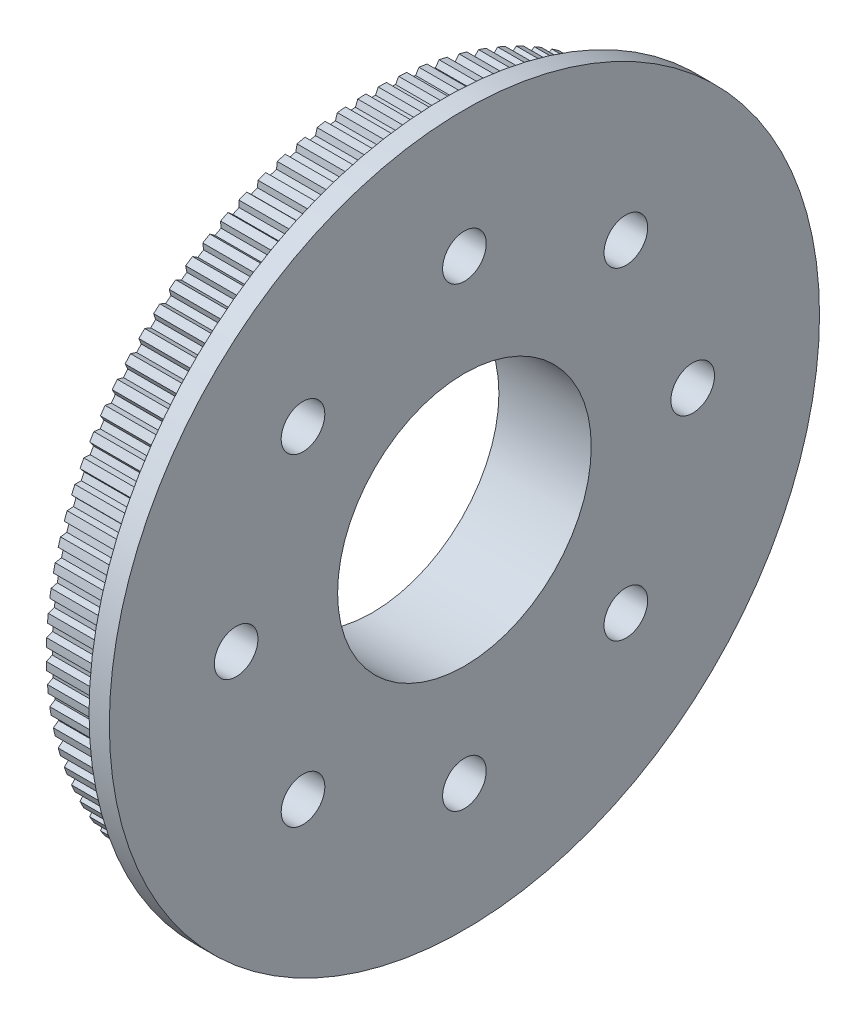
SolidWorks part; units mm, degrees
ref_plane "Front Plane" through (0, 0, 0) normal (0, 0, 1) x (1, 0, 0)
ref_plane "Top Plane" through (0, 0, 0) normal (0, 1, 0) x (1, 0, 0)
ref_plane "Right Plane" through (0, 0, 0) normal (1, 0, 0) x (0, 0, -1)
sketch "Sketch2" plane through (0, 0, 0) normal (1, 0, 0) x (0, 0, -1)
  line L3 (0, 0) -> (0, 31.5245) construction
  line L6 (0, -32.0325) -> (0, -32.35) construction
  line L7 (-0.5715, 32.0274) -> (-0.3362, 31.5227)
  line L8 (0.5715, 32.0274) -> (0.3362, 31.5227)
  line L9 (-0.5715, 32.0274) -> (-0.6449, 32.1848)
  line L10 (0.5715, 32.0274) -> (0.6449, 32.1848)
  line L12 (-0.3362, 31.5227) -> (0.3362, 31.5227)
  line L14 (0, 32.0325) -> (0, 32.35) construction
  line L15 (0, 0) -> (0, -1.143) construction
  circle A0 centre (0, 0) radius 32.35 construction
  circle A1 centre (0, 0) radius 31.5245 construction
  circle A2 centre (0, 0) radius 32.0325 construction
  arc A7 (0.6449, 32.1848) -> (-0.6449, 32.1848) centre (0, 0) ccw
  point P5 (0, 32.1913)
  dimension "D1" = 50
  dimension "D2" = 0.3175
sketch "Sketch1" plane through (0, 0, 0) normal (0, 0, 1) x (1, 0, 0)
  line L0 (-9.55, 0) -> (9.55, 0) construction
  line L1 (-9.55, 4) -> (9.55, 4)
  line L2 (-9.55, 4) -> (-9.55, 19.05)
  line L3 (-9.55, 19.05) -> (0.05, 19.05)
  line L5 (0.05, 19.05) -> (0.05, 32.1)
  line L9 (0.05, 32.1) -> (9.55, 32.1)
  line L10 (9.55, 32.1) -> (9.55, 4)
  line L12 (-4.75, 19.05) -> (-4.75, 4) construction
  point P7 (9.55, 32.1)
  dimension "Bore Size" = 8
  dimension "Overall Width" = 19.1
  dimension "Outside Width" = 9.5
  dimension "Hub Dia" = 38.1
  dimension "OD" = 64.2
revolve "Revolve1" add sketch "Sketch1" angle 360 mid plane about L0
sketch "Sketch3" plane through (0.05, 0, 0) normal (-1, 0, 0) x (0, 0, 1)
  line L3 (0.3362, 31.5227) -> (-0.3362, 31.5227) construction
  line L5 (-0.6449, 32.1848) -> (-0.3362, 31.5227)
  line L6 (-0.3362, 31.5227) -> (0.3362, 31.5227)
  line L7 (0.6449, 32.1848) -> (0.3362, 31.5227)
  arc A1 (0.6449, 32.1848) -> (-0.6449, 32.1848) centre (0, 0) ccw construction
  arc A2 (0.6449, 32.1848) -> (-0.6449, 32.1848) centre (0, 0) ccw
extrude "Cut-Extrude1" cut sketch "Sketch3" along normal through all both and the other way through all
pattern_circular "CirPattern1" count 100 over 360 about axis through (-9.55, 0, 0) along (-1, 0, 0) of "Cut-Extrude1" reverse direction yes
sketch "Sketch5" plane through (0, 0, 0) normal (0, 0, 1) x (1, 0, 0)
  point P0 (0, 0)
sketch "Sketch6" plane through (0, 0, 0) normal (0, 1, 0) x (1, 0, 0)
  line L0 (-9.55, 0) -> (-6.775, 0) construction
  line L1 (-9.55, 19.05) -> (-9.55, -19.05) construction
  line L2 (0, 0) -> (-2.775, 0) construction
  circle A0 centre (-4.775, 0) radius 2 construction
  circle A1 centre (-4.775, 0) radius 2.1
  dimension "D1" = 0.1
  dimension "SS Dia" = 4
extrude "Cut-Extrude3" cut sketch "Sketch6" along normal through all
sketch "Sketch7" plane through (0, 0, 0) normal (0, 0, 1) x (1, 0, 0)
  line L0 (-6.521, 19.05) -> (-4.775, 19.05)
  line L1 (-6.775, 18.796) -> (-6.775, 4.635)
  line L2 (-6.775, 4.635) -> (-6.521, 4.381)
  line L3 (-6.521, 4.381) -> (-4.775, 4.381)
  line L4 (-4.775, 4.381) -> (-4.775, 19.05) construction
  line L5 (-2.675, 0) -> (-6.875, 0) construction
  line L6 (-6.775, 18.796) -> (-6.521, 19.05)
  line L7 (-9.55, 19.05) -> (0.05, 19.05) construction
  line L8 (-4.775, 19.05) -> (-4.775, 4.381)
  line L9 (-2.675, 0) -> (-6.875, 0) construction
  line L10 (-4.775, 0) -> (-5.825, -1.8187) construction
  circle A0 centre (-4.775, 0) radius 2.1 construction
  point P0 (-6.775, 19.05)
  point P4 (-6.775, 4.381)
  point P17 (-5.825, -1.8187)
  dimension "D1" = 60
  dimension "D2" = 0.381
revolve "Revolve2" add sketch "Sketch7" angle 360 mid plane about L4
sketch "Sketch8" plane through (0, 19.05, 0) normal (0, 1, 0) x (1, 0, 0)
  line L1 (-4.775, 0.866) -> (-5.525, 0.433)
  line L2 (-5.525, 0.433) -> (-5.525, -0.433)
  line L3 (-5.525, -0.433) -> (-4.775, -0.866)
  line L4 (-4.775, -0.866) -> (-4.025, -0.433)
  line L5 (-4.025, -0.433) -> (-4.025, 0.433)
  line L6 (-4.025, 0.433) -> (-4.775, 0.866)
  circle A0 centre (-4.775, 0) radius 0.75 construction
  dimension "D1" = 1.5
extrude "Cut-Extrude4" cut sketch "Sketch8" against normal blind 1.016
pattern_circular "CirPattern2" count 2 over 90 about axis through (-9.55, 0, 0) along (-1, 0, 0) of "Cut-Extrude3" reverse direction yes
pattern_circular "CirPattern3" count 2 over 90 about axis through (-9.55, 0, 0) along (-1, 0, 0) reverse direction yes of bodies 107
chamfer "Chamfer1" distance 0.5 angle 45 1 edges at (-9.55, 0, 4)
chamfer "Chamfer2" distance 0.5 angle 45 1 edges at (-9.55, 0, 19.05)
chamfer "Chamfer3" distance 0.5 angle 45 1 edges at (9.55, 0, 4)
sketch "Sketch9" plane through (0, 0, 0) normal (1, 0, 0) x (0, 0, -1)
  circle A0 centre (0, 0) radius 32.1 construction
sketch "Sketch10" plane through (-9.55, 0, 0) normal (-1, 0, 0) x (0, 0, 1)
  circle A0 centre (0, 0) radius 56.9699
extrude "Cut-Extrude5" cut sketch "Sketch10" against normal blind 12
sketch "Sketch13" plane through (9.55, 0, 0) normal (1, 0, 0) x (0, 0, -1)
  circle A0 centre (0, 0) radius 35
  dimension "D1" = 70
extrude "Boss-Extrude1" add sketch "Sketch13" along normal blind 2
sketch "Sketch11" plane through (2.45, 0, 0) normal (-1, 0, 0) x (0, 0, 1)
  circle A0 centre (0, 0) radius 12.5
  dimension "D1" = 25
extrude "Cut-Extrude6" cut sketch "Sketch11" against normal through all
sketch "Sketch12" plane through (2.45, 0, 0) normal (-1, 0, 0) x (0, 0, 1)
  line L0 (0, 0) -> (0, 22.5) construction
  circle A0 centre (0, 22.5) radius 2.15
  dimension "D2" = 4.3
  dimension "D1" = 22.5
extrude "Cut-Extrude7" cut sketch "Sketch12" against normal through all
pattern_circular "CirPattern4" count 8 over 360 about axis through (2.45, 0, 0) along (-1, 0, 0) of "Cut-Extrude7"
equation "\"D2@Sketch2\"=(\"hs@Sketch2\"-\"ht@Sketch2\")/2"
